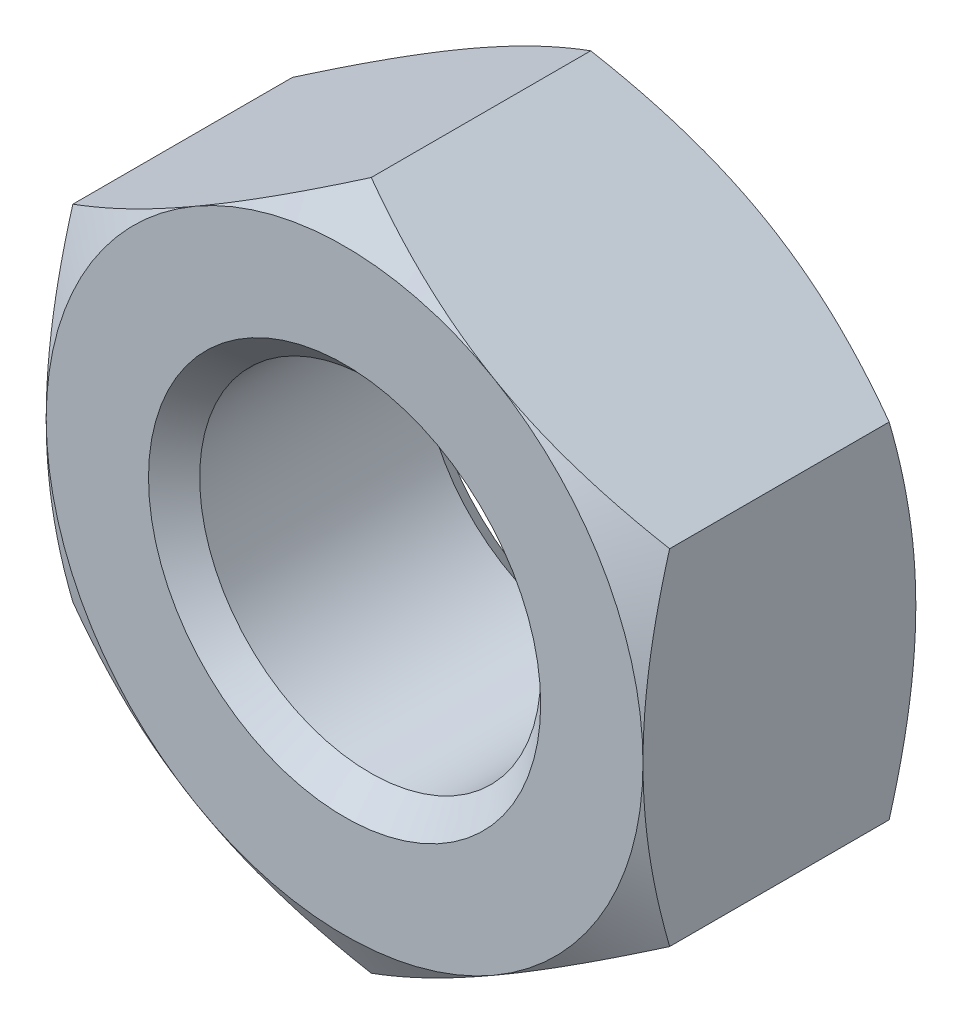
SolidWorks part; units mm, degrees
material "AISI Type A2 Tool Steel"
ref_plane "Front Plane" through (0, 0, 0) normal (0, 0, 1) x (1, 0, 0)
ref_plane "Top Plane" through (0, 0, 0) normal (0, 1, 0) x (1, 0, 0)
ref_plane "Right Plane" through (0, 0, 0) normal (1, 0, 0) x (0, 0, -1)
sketch "Sketch1" plane through (0, 0, 0) normal (0, 0, 1) x (1, 0, 0)
  line L1 (0, 4.0415) -> (-3.5, 2.0207)
  line L2 (-3.5, 2.0207) -> (-3.5, -2.0207)
  line L3 (-3.5, -2.0207) -> (0, -4.0415)
  line L4 (0, -4.0415) -> (3.5, -2.0207)
  line L5 (3.5, -2.0207) -> (3.5, 2.0207)
  line L6 (3.5, 2.0207) -> (0, 4.0415)
  circle A0 centre (0, 0) radius 3.5 construction
  circle A1 centre (0, 0) radius 2
  circle A3 centre (0, 0) radius 4.5
  dimension "D1" = 9
  dimension "D2" = 7
  dimension "D3" = 4
extrude "Boss-Extrude1" add sketch "Sketch1" along normal blind 3.2 contours A3 L6 L5 L4 L3 L2 L1 | L5 L6 L1 L2 L3 L4 A1 region at (1.6965, 2.9385, 0) region at (-4.3727, 0, 0)
chamfer "Chamfer1" distance 1 angle 30 1 edges at (4.5, 0, 3.2) first distance on face at (4.5, 0, 3.2)
chamfer "Chamfer2" distance 1 angle 30 1 edges at (4.5, 0, 0) first distance on face at (4.5, 0, 0)
extrude "Cut-Extrude1" cut sketch "Sketch1<3>" along normal through all contours A3 L6 L5 L4 L3 L2 L1 region at (-4.3727, 0, 0)
sketch "Sketch1<3>" plane through (0, 0, 0) normal (0, 0, 1) x (1, 0, 0) same geometry as "Sketch1"
chamfer "Chamfer3" distance 0.3 angle 45 2 edges at (2, 0, 0) (2, 0, 3.2)
